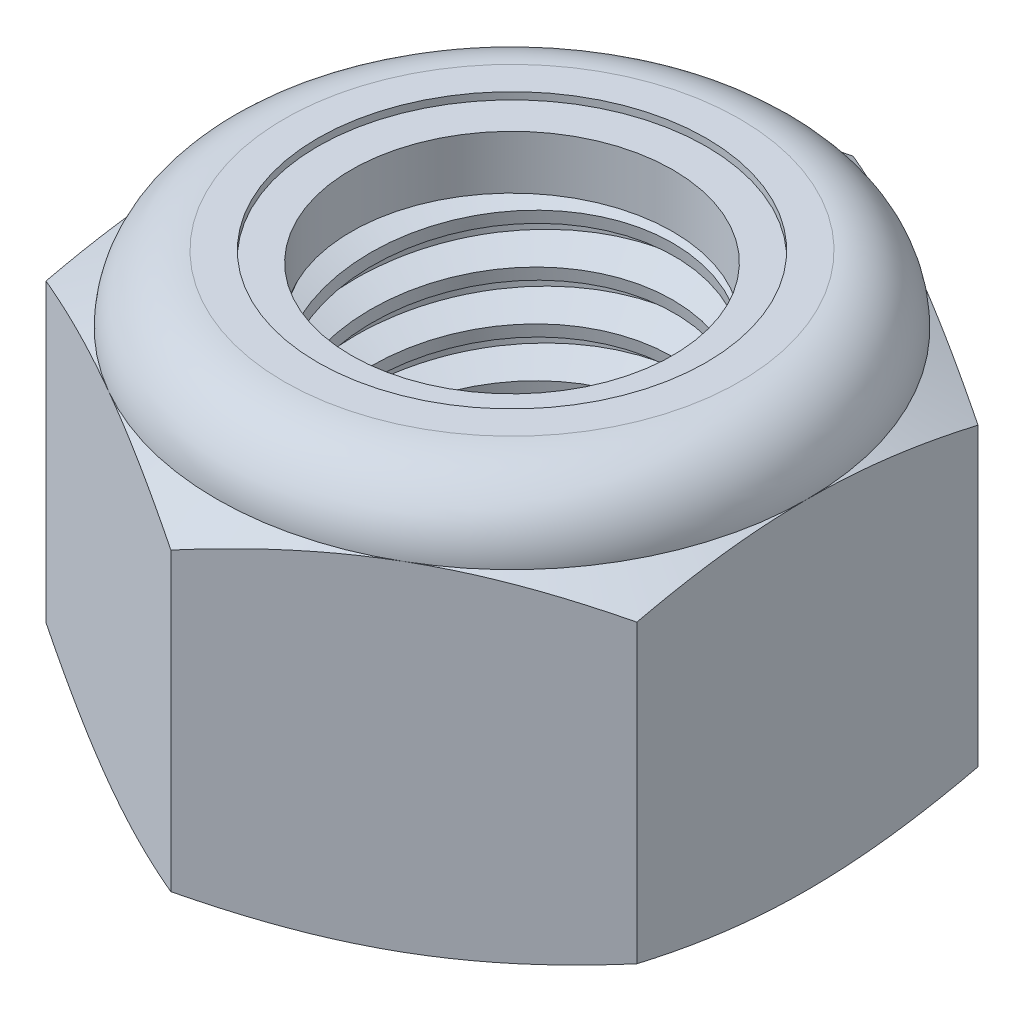
SolidWorks part; units mm, degrees
ref_plane "Front" through (0, 0, 0) normal (0, 0, 1) x (1, 0, 0)
ref_plane "Top" through (0, 0, 0) normal (0, 1, 0) x (1, 0, 0)
ref_plane "Right" through (0, 0, 0) normal (1, 0, 0) x (0, 0, -1)
sketch "Sketch1" plane through (0, 0, 0) normal (0, 1, 0) x (1, 0, 0)
  line L1 (0, 7.3323) -> (-6.35, 3.6662)
  line L2 (-6.35, 3.6662) -> (-6.35, -3.6662)
  line L3 (-6.35, -3.6662) -> (0, -7.3323)
  line L4 (0, -7.3323) -> (6.35, -3.6662)
  line L5 (6.35, -3.6662) -> (6.35, 3.6662)
  line L6 (6.35, 3.6662) -> (0, 7.3323)
  circle A0 centre (0, 0) radius 6.35 construction
  dimension "Hex Flats" = 12.7
extrude "Extrude1" add sketch "Sketch1" along normal blind 8.7312
sketch "Sketch2" plane through (0, 0, 0) normal (1, 0, 0) x (0, 0, -1)
  line L0 (-3.9624, 0) -> (-3.9624, 8.7312) construction
  line L1 (0, 0) -> (3.9624, 0)
  line L2 (0, 0) -> (0, 8.7312)
  line L3 (0, 8.7312) -> (3.9624, 8.7312)
  line L4 (3.9624, 0) -> (3.9624, 8.7312)
  line L5 (-3.6662, 8.7312) -> (3.6662, 8.7312) construction
  line L7 (0, -3.9624) -> (0, 0) construction
  dimension "Thread Dia" = 7.9248
revolve "Revolve1" add sketch "Sketch2" angle 360 about L7
sketch "Sketch3" plane through (0, 0, 0) normal (1, 0, 0) x (0, 0, -1)
  line L0 (3.9624, 8.7312) -> (-3.9624, 8.7312) construction
  line L1 (-3.9624, 8.7312) -> (-3.9624, 7.6729) construction
  line L2 (-3.9624, 7.6729) -> (3.9624, 8.7312) construction
  line L3 (3.9624, 8.7312) -> (3.9799, 8.6001) construction
  line L4 (3.9799, 8.6001) -> (4.1025, 7.6822)
  line L5 (4.1025, 7.6822) -> (3.4909, 7.9342)
  line L6 (3.4909, 7.9342) -> (3.4559, 8.1965)
  line L7 (3.4559, 8.1965) -> (3.9799, 8.6001)
  line L8 (3.4734, 8.0653) -> (4.0412, 8.1412) construction
  line L9 (3.9624, 8.7312) -> (3.9624, 8.1307) construction
  line L10 (3.9624, 8.1307) -> (-3.9624, 7.0723) construction
  line L11 (-3.9624, 7.0723) -> (-3.9624, 7.6729) construction
  line L12 (-0.1509, 8.7312) -> (0.1509, 6.4717) construction
  line L13 (-3.9624, 0) -> (-3.9624, 8.7312) construction
  line L14 (0, 8.7312) -> (3.9624, 8.7312) construction
  line L15 (3.9624, 0) -> (3.9624, 8.7312) construction
  point P13 (0, 7.6015)
  dimension "D1" = 0.1323
  dimension "D2" = 0.2646
  dimension "Thread Pitch" = 1.0583
  dimension "D4" = 60
  dimension "D5" = 1.0583
revolve "Cut-Revolve1" cut sketch "Sketch3" angle 360 about L12
pattern_linear "LPattern1" count 8 spacing 1.0583 along (0, -1, 0) count 2 spacing 1.0583 along (0, 1, 0) of "Cut-Revolve1"
sketch "Sketch4" plane through (0, 0, 0) normal (1, 0, 0) x (0, 0, -1)
  line L0 (0, 8.7312) -> (3.9624, 8.7312)
  line L1 (3.9624, 8.7312) -> (3.4559, 8.4951)
  line L2 (3.4559, 8.4951) -> (3.4559, 0.2362)
  line L3 (3.4559, 0.2362) -> (3.9624, 0)
  line L4 (3.9624, 0) -> (0, 0)
  line L5 (0, 0) -> (0, 8.7312)
  line L6 (3.9624, 0) -> (3.9624, 8.7312) construction
  line L7 (0, 8.7312) -> (3.9624, 8.7312) construction
  line L8 (0, 0) -> (3.9624, 0) construction
  line L9 (0, 0) -> (0, 8.7312) construction
  line L10 (0, 8.7312) -> (0, 9.2901) construction
  dimension "D1" = 25
revolve "Cut-Revolve2" cut sketch "Sketch4" angle 360 about L10
combine bodies "Combine1" operation type subtract main body 112 bodies to subtract 111
sketch "Sketch5" plane through (0, 0, 0) normal (1, 0, 0) x (0, 0, -1)
  line L0 (0, 0) -> (6.35, 0)
  line L1 (6.35, 0) -> (7.3323, 0.4581)
  line L2 (7.3323, 0.4581) -> (7.3323, 6.818)
  line L3 (7.3323, 6.818) -> (6.35, 7.276)
  line L4 (4.8948, 8.7312) -> (4.8948, 10.0012)
  line L5 (4.8948, 10.0012) -> (8.6023, 10.0012)
  line L6 (8.6023, 10.0012) -> (8.6023, -1.27)
  line L7 (8.6023, -1.27) -> (0, -1.27)
  line L8 (0, -1.27) -> (0, 0)
  line L9 (6.35, 7.276) -> (6.35, 0) construction
  line L10 (0, 0) -> (3.9624, 0) construction
  line L13 (7.3323, 3.638) -> (8.6023, 3.638) construction
  line L14 (7.3323, 8.7312) -> (7.3323, 0) construction
  line L15 (0, 0) -> (0, 10.0012) construction
  line L20 (0, 10.0012) -> (4.8948, 10.0012) construction
  line L22 (0, 8.7312) -> (3.9624, 8.7312) construction
  arc A0 (6.35, 7.276) -> (4.8948, 8.7312) centre (4.8948, 7.276) ccw
  dimension "D1" = 25
  dimension "D2" = 1.27
  dimension "D3" = 8.7312
  dimension "D4" = 1.4552
revolve "Cut-Revolve3" cut sketch "Sketch5" angle 360 about L15
sketch "Sketch6" plane through (0, 0, 0) normal (1, 0, 0) x (0, 0, -1)
  line L0 (0, 7.276) -> (6.1976, 7.276)
  line L1 (4.8948, 8.5788) -> (4.1753, 8.5788)
  line L2 (0, 10.0012) -> (0, 7.276)
  line L3 (4.1753, 10.0012) -> (0, 10.0012)
  line L4 (0, 10.0012) -> (4.8948, 10.0012) construction
  line L5 (0, 0) -> (0, 10.0012) construction
  line L6 (0, 10.0012) -> (0, 44.323) construction
  line L7 (4.1753, 8.5788) -> (4.1753, 10.0012)
  line L8 (4.8948, 8.7312) -> (4.8948, 8.5788) construction
  line L9 (4.1753, 8.5788) -> (3.4559, 8.5788) construction
  line L10 (3.4559, 8.5788) -> (3.4559, 8.4951) construction
  arc A0 (6.1976, 7.276) -> (4.8948, 8.5788) centre (4.8948, 7.276) ccw
  arc A1 (6.35, 7.276) -> (4.8948, 8.7312) centre (4.8948, 7.276) ccw construction
  dimension "D1" = 0.1524
revolve "Cut-Revolve4" cut sketch "Sketch6" angle 360 about L6
sketch "Sketch7" plane through (0, 0, 0) normal (1, 0, 0) x (0, 0, -1)
  line L0 (3.4559, 7.3522) -> (6.119, 7.3522)
  line L1 (4.8948, 8.5026) -> (3.4559, 8.5026)
  line L2 (3.4559, 8.5026) -> (3.4559, 7.3522)
  line L3 (3.4559, 7.3522) -> (0, 7.3522) construction
  line L4 (0, 7.3522) -> (0, 8.5026) construction
  line L5 (0, 8.5026) -> (3.4559, 8.5026) construction
  line L6 (3.4559, 7.3522) -> (3.4559, 7.276) construction
  line L7 (0, 7.276) -> (6.1976, 7.276) construction
  line L8 (4.8948, 8.5026) -> (4.8948, 8.5788) construction
  arc A0 (6.119, 7.3522) -> (4.8948, 8.5026) centre (4.8948, 7.276) ccw
  arc A2 (6.1976, 7.276) -> (4.8948, 8.5788) centre (4.8948, 7.276) ccw construction
  dimension "D1" = 0.0762
revolve "Revolve2" add sketch "Sketch7" angle 360 about L4
equation "\"D1@Sketch3\"=\"Thread Pitch@Sketch3\"/8"
equation "\"D2@Sketch3\"=\"Thread Pitch@Sketch3\"/4"
equation "\"D5@Sketch3\"=\"Thread Pitch@Sketch3\""
equation "\"D4@LPattern1\"=\"Thread Pitch@Sketch3\""
equation "\"D3@LPattern1\"=\"Thread Pitch@Sketch3\""
equation "\"D1@LPattern1\"=\"Height@Extrude1\"/\"Thread Pitch@Sketch3\""
equation "\"D4@Sketch5\"=\"Height@Extrude1\"/6"
